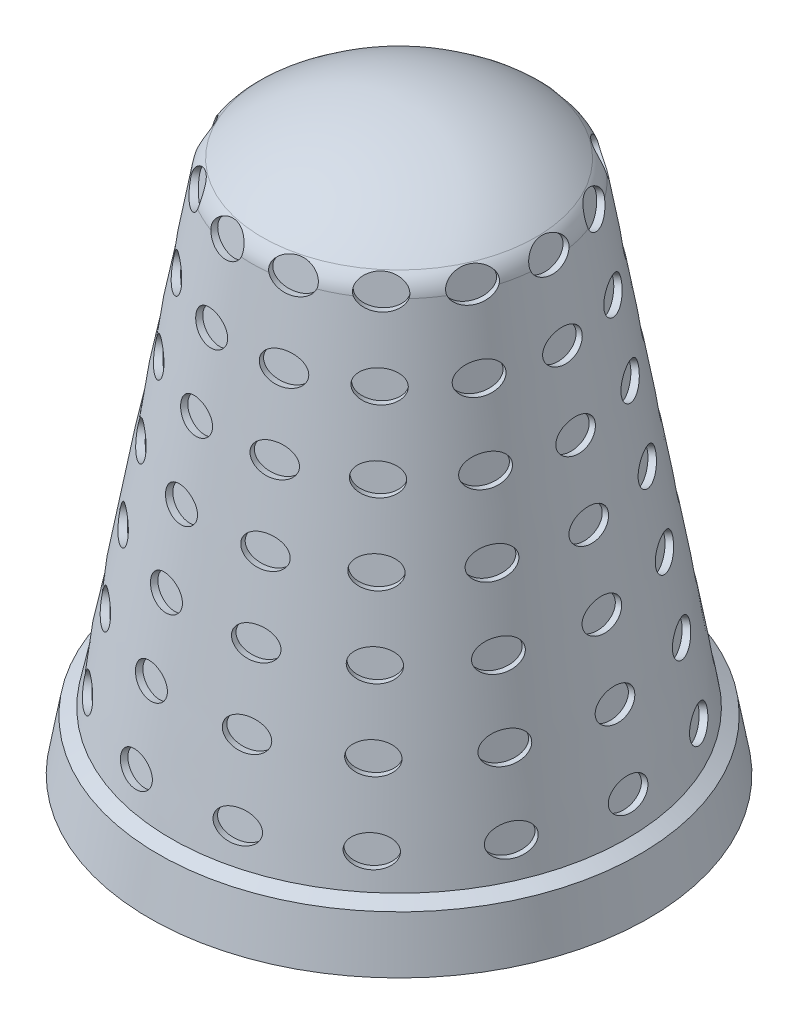
SolidWorks part; units mm, degrees
ref_plane "Front Plane" through (0, 0, 0) normal (0, 0, 1) x (1, 0, 0)
ref_plane "Top Plane" through (0, 0, 0) normal (0, 1, 0) x (1, 0, 0)
ref_plane "Right Plane" through (0, 0, 0) normal (1, 0, 0) x (0, 0, -1)
sketch "Sketch1" plane through (0, 0, 0) normal (0, 0, 1) x (1, 0, 0)
  line L0 (0, 0) -> (0, 40) construction
  line L1 (0, 40) -> (12.2218, 40) construction
  line L2 (-10, 36.1803) -> (-15.6743, 4)
  line L3 (-13.3333, 0) -> (-6.9537, 36.1803)
  line L4 (-15.6743, 4) -> (-16.5403, 3.5)
  line L5 (-17.1574, 0) -> (-16.5403, 3.5)
  line L6 (-17.1574, 0) -> (-13.3333, 0)
  line L10 (0, 40) -> (0, 38.1664)
  arc A0 (0, 40) -> (-10, 36.1803) centre (0, 25) ccw
  arc A1 (-6.9537, 36.1803) -> (0, 38.1664) centre (0, 25) cw
  dimension "D4" = 10
  dimension "D5" = 15
  dimension "D14" = 0.6171
  dimension "D1" = 3
  dimension "D2" = 40
  dimension "D3" = 80
  dimension "D6" = 3.5
  dimension "D7" = 30
  dimension "D8" = 4
revolve "Revolve1" add sketch "Sketch1" angle 360 about L0
fillet "Fillet1" radius 2 1 edges at (0, 36.1803, -10)
ref_plane "Plane1" through (-15.8857, 2.8011, 0) normal (-0.9848, 0.1736, 0) x (0, 0, 1)
ref_axis "Axis1" through (0, 0, 0) along (0, 1, 0)
sketch "Sketch2" plane through (-15.8857, 2.8011, 0) normal (-0.9848, 0.1736, 0) x (0, 0, 1)
  line L0 (0, 0) -> (0, 3.4468) construction
  circle A0 centre (0, 3.4392) radius 1 construction
  ellipse E0 centre (0, 3.4392) end of major axis (1.4, 3.4392) minor radius 1
  ellipse E1 centre (0, 3.9392) end of major axis (-15.6743, 3.9392) minor radius 2.7218 construction
  dimension "D1" = 2
  dimension "D2" = 0.5
  dimension "D3" = 1.4
extrude "Cut-Extrude1" cut sketch "Sketch2" against normal blind 0.5
ref_plane "Plane2" through (0, 0, 0) normal (0, 0, -1) x (0, 1, 0)
sketch "Sketch4" plane through (0, 0, 0) normal (0, 1, 0) x (1, 0, 0)
  line L0 (0, 0) -> (17.1574, 0)
  line L1 (1.925, 0) -> (-1.925, 0) construction
  circle A0 centre (0, 0) radius 17.1574 construction
sketch "Sketch6" plane through (0, 0, 0) normal (0, 0, -1) x (0, 1, 0)
  line L0 (0, 0) -> (3, 0)
  line L1 (0, 0) -> (0, 17.1574) construction
  line L2 (3, 0) -> (3, 16.6285)
  line L3 (3.5, 16.5403) -> (0, 17.1574) construction
  dimension "D1" = 3
ref_axis "Axis2" through (17.1574, 0, 0) along (-0.9851, 0.1722, 0)
sketch "Sketch7" plane through (0, 0, 0) normal (0, 0, 1) x (1, 0, 0)
  line L0 (-10.1251, 35.4709) -> (-15.1148, 7.1728) construction
  line L1 (-10.1251, 35.4709) -> (-15.1148, 7.1728) construction
pattern_linear "LPattern1" count 7 spacing 5 along (0.1736, 0.9848, 0) of "Cut-Extrude1"
pattern_circular "CirPattern1" count 14 every 26 about axis through (0, 36.1803, 0) along (0, 1, 0) of "LPattern1"
